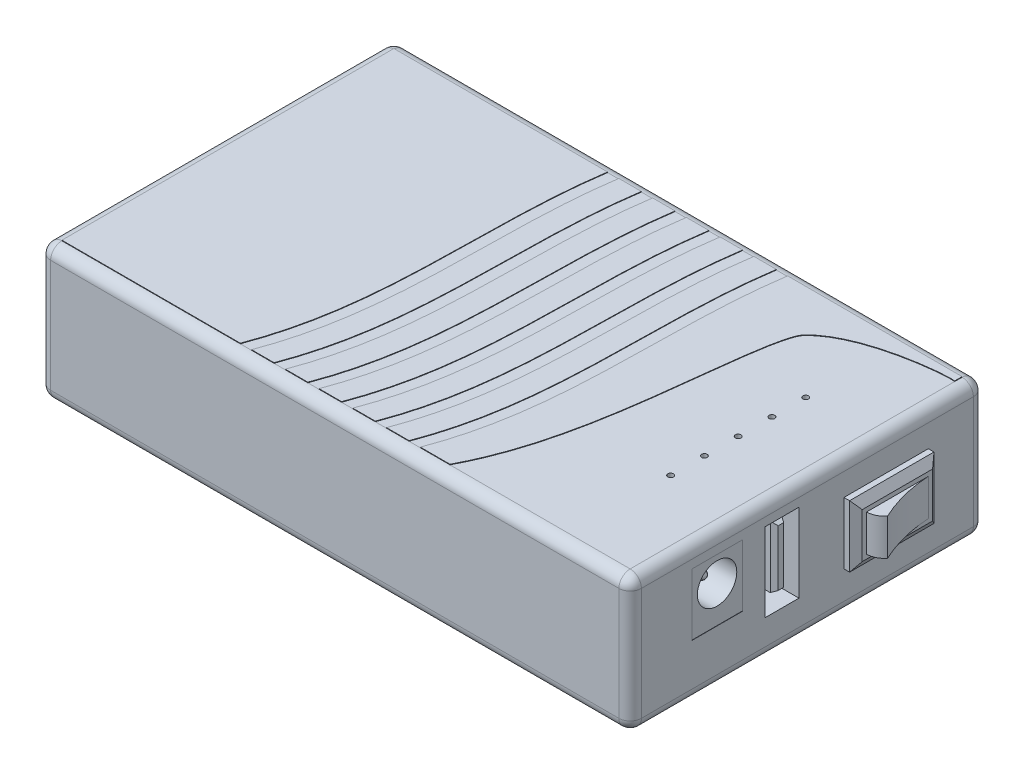
SolidWorks part; units mm, degrees
note: The reader was unsure of these and kept them because the rebuilt part matched: shared geometry of "Sketch3<3>", "Sketch3<4>".
material "ABS"
ref_plane "Front Plane" through (0, 0, 0) normal (0, 0, 1) x (1, 0, 0)
ref_plane "Top Plane" through (0, 0, 0) normal (0, 1, 0) x (1, 0, 0)
ref_plane "Right Plane" through (0, 0, 0) normal (1, 0, 0) x (0, 0, -1)
sketch "Sketch2" plane through (0, 0, 0) normal (0, 1, 0) x (1, 0, 0)
  line L1 (0, 63) -> (105, 63)
  line L2 (0, 63) -> (0, 0)
  line L3 (0, 0) -> (105, 0)
  line L4 (105, 63) -> (105, 0)
  dimension "D1" = 105
  dimension "D2" = 63
extrude "Boss-Extrude1" add sketch "Sketch2" along normal blind 24 contours L1 L4 L3 L2
sketch "Sketch3" plane through (105, 0, 0) normal (1, 0, 0) x (0, 0, -1)
  line L0 (63, 24) -> (0, 24) construction
  line L1 (38, 18) -> (53, 18)
  line L2 (38, 18) -> (38, 7)
  line L3 (38, 7) -> (53, 7)
  line L4 (53, 18) -> (53, 7)
  line L5 (63, 24) -> (63, 0) construction
  line L7 (24, 20.5) -> (30, 20.5)
  line L8 (24, 20.5) -> (24, 6.5)
  line L9 (24, 6.5) -> (30, 6.5)
  line L10 (30, 20.5) -> (30, 6.5)
  line L11 (11, 20.5) -> (20, 20.5)
  line L12 (11, 20.5) -> (11, 9.5)
  line L13 (11, 9.5) -> (20, 9.5)
  line L14 (20, 20.5) -> (20, 9.5)
  dimension "D1" = 15
  dimension "D2" = 11
  dimension "D3" = 6
  dimension "D4" = 25
  dimension "D5" = 14
  dimension "D6" = 6
  dimension "D7" = 3.5
  dimension "D8" = 8
  dimension "D9" = 19
  dimension "D10" = 9
  dimension "D11" = 11
extrude "Cut-Extrude1" cut sketch "Sketch3" against normal blind 0.05 contours L13 L14 L11 L12
extrude "Cut-Extrude2" cut sketch "Sketch3<3>" against normal blind 11 contours L9 L10 L7 L8
sketch "Sketch3<3>" plane through (105, 0, 0) normal (1, 0, 0) x (0, 0, -1) same geometry as "Sketch3"
extrude "Boss-Extrude2" add sketch "Sketch3<4>" along normal blind 1 contours L1 L4 L3 L2
sketch "Sketch3<4>" plane through (105, 0, 0) normal (1, 0, 0) x (0, 0, -1) same geometry as "Sketch3"
ref_plane "Plane1" through (107, 0, 0) normal (1, 0, 0) x (0, 0, -1)
sketch "Sketch5" plane through (107, 0, 0) normal (1, 0, 0) x (0, 0, -1)
  line L1 (39.25, 16.5) -> (51.75, 16.5)
  line L2 (39.25, 16.5) -> (39.25, 8.5)
  line L3 (39.25, 8.5) -> (51.75, 8.5)
  line L4 (51.75, 16.5) -> (51.75, 8.5)
  dimension "D1" = 12.5
  dimension "D2" = 8
  dimension "D3" = 39.25
  dimension "D4" = 8.5
loft "Loft3" add profiles "Sketch5" section face at (106, 12.5, -45.5) section "Sketch5"
sketch "Sketch6" plane through (107, 0, 0) normal (1, 0, 0) x (0, 0, -1)
  line L0 (51, 15.75) -> (51.75, 16.5) construction
  line L1 (40, 15.75) -> (51, 15.75)
  line L2 (40, 15.75) -> (40, 9.25)
  line L3 (40, 9.25) -> (51, 9.25)
  line L4 (51, 15.75) -> (51, 9.25)
  line L5 (51, 9.25) -> (51.75, 8.5) construction
  line L6 (39.25, 8.5) -> (40, 9.25) construction
  line L7 (39.25, 16.5) -> (40, 15.75) construction
  dimension "D1" = 11
  dimension "D2" = 6.5
extrude "Boss-Extrude3" add sketch "Sketch6" along normal blind 2.5
sketch "Sketch8" plane through (0, 9.25, 0) normal (0, -1, 0) x (1, 0, 0)
  line L0 (109.5, -40) -> (109.5, -51) construction
  line L1 (107, -55) -> (107, 55) construction
  line L2 (109.5, -40) -> (107, -40) construction
  line L3 (109.5, -51) -> (107, -51) construction
  line L5 (107, -51) -> (109.5, -51)
  line L6 (109.5, -51) -> (109.5, -41.25)
  line L7 (109.5, -40) -> (107, -40)
  arc A0 (109.5, -41.25) -> (107, -40) centre (106.8373, -43.4504) ccw
  arc A1 (109.5, -41.25) -> (107, -51) centre (133.1795, -52.5172) ccw
  line M2 (107, -51) -> (109.5, -51)
  line M3 (109.5, -51) -> (109.5, -40)
  line M4 (109.5, -40) -> (107, -40)
  dimension "D1" = 1.25
  dimension "D2" = 3.4542
  dimension "D3" = 26.2235
extrude "Cut-Extrude3" cut sketch "Sketch8" against normal through all contours A0 M3 M4 | A1 M3 M2
fillet "Fillet1" radius 2 12 edges at (0, 12, 0) (0, 0, -31.5) (0, 24, -31.5) (0, 12, -63) (52.5, 24, -63) (52.5, 0, -63) (105, 12, -63) (105, 0, -31.5) (105, 24, -31.5) (105, 12, 0) (52.5, 0, 0) (52.5, 24, 0)
sketch "Sketch9" plane through (104.95, 0, 0) normal (1, 0, 0) x (0, 0, -1)
  line L0 (11, 9.5) -> (20, 9.5) construction
  circle A0 centre (15.5, 16) radius 3.5
  point P6 (15.5, 9.5)
  dimension "D1" = 7
  dimension "D2" = 6.5
extrude "Cut-Extrude4" cut sketch "Sketch9" against normal blind 10
sketch "Sketch10" plane through (0, 24, 0) normal (0, 1, 0) x (1, 0, 0)
  line L0 (103, 2) -> (103, 61) construction
  line L1 (82.6052, 53.4226) -> (80.4654, 51.6767) construction
  line L2 (80.4654, 51.6767) -> (78.9818, 35.0606) construction
  line L3 (78.9818, 35.0606) -> (78.9818, 17.1587) construction
  line L4 (78.9818, 17.1587) -> (70.9705, 2) construction
  line L5 (2, 2) -> (103, 2) construction
  line L6 (70.9705, 2) -> (65.7071, 2)
  line L7 (103, 61) -> (2, 61) construction
  line L8 (71.9946, 61) -> (103, 61)
  line L9 (103, 61) -> (103, 59.6885)
  line L10 (63.7071, 2) -> (59.7071, 2)
  line L11 (69.9946, 61) -> (65.9946, 61)
  line L12 (63.9946, 61) -> (59.9946, 61)
  line L13 (57.7071, 2) -> (53.7071, 2)
  line L14 (57.9946, 61) -> (53.9946, 61)
  line L15 (51.7071, 2) -> (47.7071, 2)
  line L16 (51.9946, 61) -> (47.9946, 61)
  line L17 (45.7071, 2) -> (41.7071, 2)
  line L18 (45.9946, 61) -> (41.9946, 61)
  line L19 (39.7071, 2) -> (35.7071, 2)
  line L20 (33.7071, 2) -> (2, 2)
  line L21 (2, 2) -> (2, 61)
  line L22 (2, 61) -> (39.9946, 61)
  spline S0 degree 3 poles (103, 59.6885) (100.7932, 59.9378) (87.3686, 58.5976) (82.6052, 53.4226) knots 0 0 0 0 1 1 1 1
  spline S1 degree 4 poles (82.6052, 53.4226) (80.4654, 51.6767) (78.9818, 35.0606) (78.9818, 17.1587) (70.9705, 2) knots 0 0 0 0 0 1 1 1 1 1
  spline S2 degree 3 poles (65.7071, 2) (72.9066, 21.0872) (69.0437, 41.3506) (71.9946, 61) knots 0 0 0 0 1 1 1 1
  spline S3 degree 3 poles (59.7071, 2) (66.9066, 21.0872) (63.0437, 41.3506) (65.9946, 61) knots 0 0 0 0 1 1 1 1
  spline S4 degree 3 poles (53.7071, 2) (60.9066, 21.0872) (57.0437, 41.3506) (59.9946, 61) knots 0 0 0 0 1 1 1 1
  spline S5 degree 3 poles (47.7071, 2) (54.9066, 21.0872) (51.0437, 41.3506) (53.9946, 61) knots 0 0 0 0 1 1 1 1
  spline S6 degree 3 poles (41.7071, 2) (48.9066, 21.0872) (45.0437, 41.3506) (47.9946, 61) knots 0 0 0 0 1 1 1 1
  spline S7 degree 3 poles (35.7071, 2) (42.9066, 21.0872) (39.0437, 41.3506) (41.9946, 61) knots 0 0 0 0 1 1 1 1
  spline S8 degree 3 poles (63.7071, 2) (70.9066, 21.0872) (67.0437, 41.3506) (69.9946, 61) knots 0 0 0 0 1 1 1 1
  spline S9 degree 3 poles (57.7071, 2) (64.9066, 21.0872) (61.0437, 41.3506) (63.9946, 61) knots 0 0 0 0 1 1 1 1
  spline S10 degree 3 poles (51.7071, 2) (58.9066, 21.0872) (55.0437, 41.3506) (57.9946, 61) knots 0 0 0 0 1 1 1 1
  spline S11 degree 3 poles (45.7071, 2) (52.9066, 21.0872) (49.0437, 41.3506) (51.9946, 61) knots 0 0 0 0 1 1 1 1
  spline S12 degree 3 poles (39.7071, 2) (46.9066, 21.0872) (43.0437, 41.3506) (45.9946, 61) knots 0 0 0 0 1 1 1 1
  spline S13 degree 3 poles (33.7071, 2) (40.9066, 21.0872) (37.0437, 41.3506) (39.9946, 61) knots 0 0 0 0 1 1 1 1
extrude "Boss-Extrude4" add sketch "Sketch10" along normal blind 0.1 contours L22 S13 L20 L21 | L19 S7 L18 S12 | L17 S6 L16 S11 | L15 S5 L14 S10 | L13 S4 L12 S9 | L11 S3 L10 S8 | L9 S0 S1 L6 S2 L8
sketch "Sketch11" plane through (0, 24, 0) normal (0, 1, 0) x (1, 0, 0)
  line L0 (103, 0) -> (2, 0) construction
  line L1 (105, 61) -> (105, 2) construction
  line L2 (70.9705, 2) -> (103, 2) construction
  circle A0 centre (92.2, 20) radius 0.5
  circle A1 centre (92.2, 26) radius 0.5
  circle A2 centre (92.2, 32) radius 0.5
  circle A3 centre (92.2, 38) radius 0.5
  circle A4 centre (92.2, 44) radius 0.5
  dimension "D1" = 1
  dimension "D3" = 12.8
  dimension "D2" = 20
  dimension "D5" = 24
  dimension "D4" = 5
extrude "Cut-Extrude5" cut sketch "Sketch11" against normal blind 1
sketch "Sketch12" plane through (0, 0, 0) normal (0, -1, 0) x (1, 0, 0)
  line L0 (2, 0) -> (103, 0) construction
  line L1 (105, -2) -> (105, -61) construction
  line L2 (103, -63) -> (2, -63) construction
  circle A0 centre (99, -6) radius 2.5
  circle A1 centre (99, -57) radius 2.5
  dimension "D1" = 5
  dimension "D2" = 6
  dimension "D3" = 6
  dimension "D5" = 6
  dimension "D4" = 2
ref_plane "Plane2" through (52.5, 0, 0) normal (1, 0, 0) x (0, 0, -1)
extrude "Cut-Extrude6" cut sketch "Sketch12" against normal blind 5 contours A1 | A0
mirror "Mirror1" about plane through (52.5, 0, 0) normal (1, 0, 0) of "Cut-Extrude6"
sketch "Sketch13" plane through (0, 0, 0) normal (0, -1, 0) x (1, 0, 0)
  line L0 (2, -2) -> (2, -61) construction
  line L1 (33, -11) -> (90, -11)
  line L2 (31, -13) -> (31, -50)
  line L3 (33, -52) -> (90, -52)
  line L4 (92, -13) -> (92, -50)
  line L5 (105, -2) -> (105, -61) construction
  arc A0 (90, -11) -> (92, -13) centre (90, -13) cw
  arc A1 (90, -52) -> (92, -50) centre (90, -50) ccw
  arc A2 (31, -50) -> (33, -52) centre (33, -50) ccw
  arc A3 (33, -11) -> (31, -13) centre (33, -13) ccw
  point P6 (2, -31.5)
  point P7 (31, -31.5)
  point P12 (92, -11)
  point P17 (31, -52)
  point P20 (31, -11)
  dimension "D4" = 2
  dimension "D1" = 61
  dimension "D2" = 41
  dimension "D3" = 13
extrude "Cut-Extrude7" cut sketch "Sketch13" against normal blind 0.05
sketch "Sketch14" plane through (94.95, 0, 0) normal (1, 0, 0) x (0, 0, -1)
  circle A0 centre (15.5, 16) radius 0.75
  circle A1 centre (15.5, 16) radius 3.5 construction
  dimension "D1" = 1.5
extrude "Boss-Extrude5" add sketch "Sketch14" along normal blind 8
fillet "Fillet2" radius 0.75 1 edges at (102.95, 16, -16.25)
sketch "Sketch15" plane through (94, 0, 0) normal (1, 0, 0) x (0, 0, -1)
  line L0 (24, 20.5) -> (30, 20.5) construction
  line L1 (26.8, 19) -> (28.8, 19)
  line L2 (26.8, 19) -> (26.8, 8)
  line L3 (26.8, 8) -> (28.8, 8)
  line L4 (28.8, 19) -> (28.8, 8)
  line L5 (24, 6.5) -> (30, 6.5) construction
  line L6 (30, 20.5) -> (30, 6.5) construction
  dimension "D1" = 1.5
  dimension "D2" = 1.5
  dimension "D3" = 2
  dimension "D4" = 1.2
extrude "Boss-Extrude6" add sketch "Sketch15" along normal blind 10 contours L3 L4 L1 L2
chamfer "Chamfer2" distance 0.9 angle 30 4 edges at (104, 13.5, -28.8) (104, 19, -27.8) (104, 8, -27.8) (104, 13.5, -26.8) first distance on face at (99, 13.5, -28.8) first distance on face at (99, 19, -27.8) first distance on face at (99, 8, -27.8) first distance on face at (99, 13.5, -26.8)
